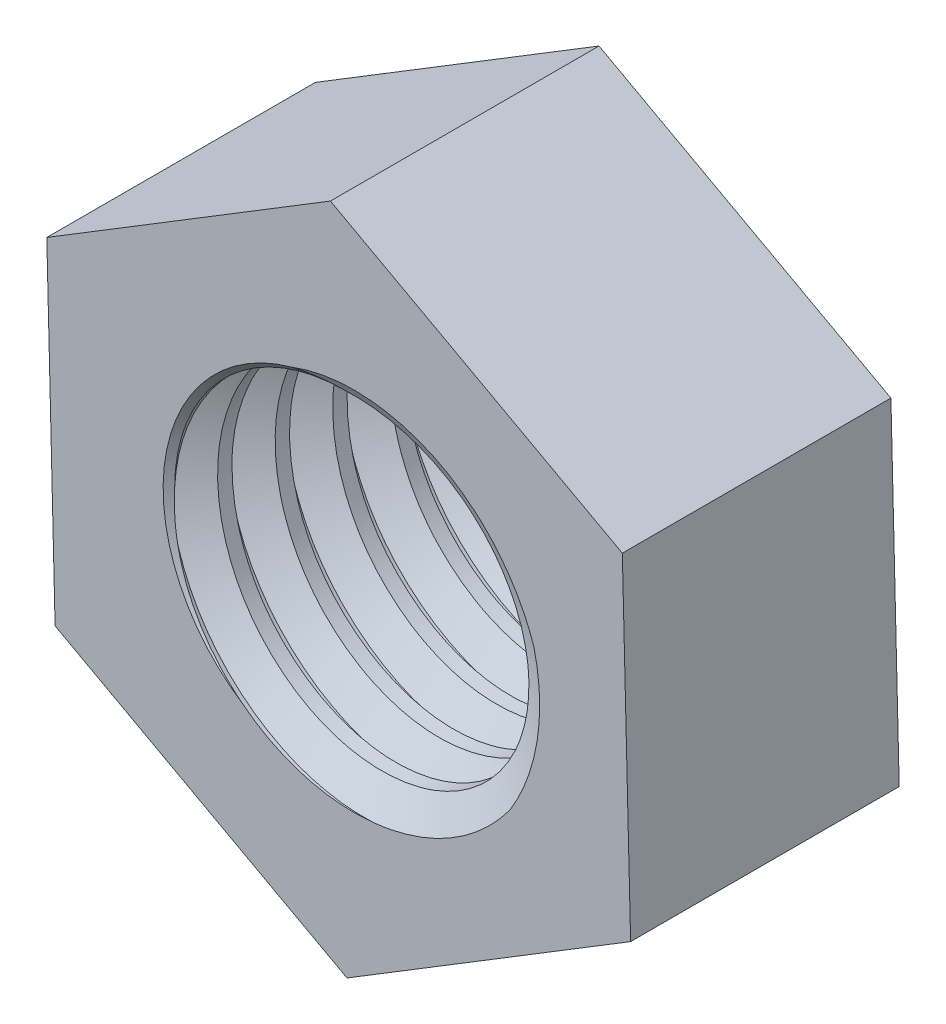
SolidWorks part; units mm, degrees
ref_plane "Front Plane" through (0, 0, 0) normal (0, 0, 1) x (1, 0, 0)
ref_plane "Top Plane" through (0, 0, 0) normal (0, 1, 0) x (1, 0, 0)
ref_plane "Right Plane" through (0, 0, 0) normal (1, 0, 0) x (0, 0, -1)
sketch "Sketch1" plane through (0, 0, 0) normal (0, 0, 1) x (1, 0, 0)
  line L1 (4.9265, 3.0105) -> (-0.1439, 5.7717)
  line L2 (-0.1439, 5.7717) -> (-5.0704, 2.7612)
  line L3 (-5.0704, 2.7612) -> (-4.9265, -3.0105)
  line L4 (-4.9265, -3.0105) -> (0.1439, -5.7717)
  line L5 (0.1439, -5.7717) -> (5.0704, -2.7612)
  line L6 (5.0704, -2.7612) -> (4.9265, 3.0105)
  circle A1 centre (0, 0) radius 2.95
  dimension "D1" = 10
extrude "Boss-Extrude1" add sketch "Sketch1" along normal blind 4.6653
sketch "Sketch2" plane through (0, 0, 4.6653) normal (0, 0, 1) x (1, 0, 0)
  circle A0 centre (0, 0) radius 5
chamfer "Chamfer2" distance 0.1 angle 45 1 edges at (2.95, 0, 0)
chamfer "Chamfer3" distance 0.1 angle 45 1 edges at (2.95, 0, 4.6653)
thread "Thread3" pitch 1 method cut profile "Thread Profile3" start angle 0, offset 3, length 10, pitch 1, diameter 5.9
ref_plane "Plane3" through (-2.95, 0, 7.5653) normal (0, -1, 0) x (-1, 0, 0)
sketch "Thread Profile3" plane through (-2.95, 0, 7.5653) normal (0, -1, 0) x (-1, 0, 0)
  line L0 (0, 0) -> (0, 1) construction
  line L1 (0, 0) -> (0.5413, 0.3125)
  line L2 (0.5413, 0.3125) -> (0.5413, 0.4375)
  line L3 (0.5413, 0.4375) -> (0, 0.75)
  line L4 (0.5413, 0.375) -> (0, 0.375) construction
  line L11 (0, 0) -> (0, 0.75)
  point P2 (0, 0)
  dimension "Pitch" = 1
  dimension "Profile_Angle" = 60
  dimension "Profile_Land" = 0.125
  dimension "Profile_Height" = 0.5413
